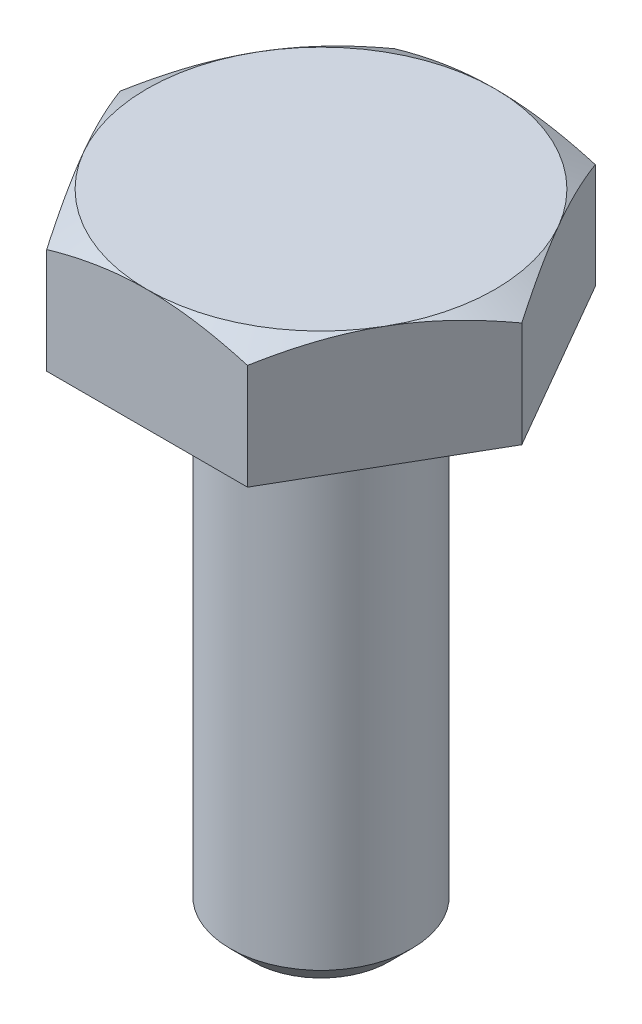
SolidWorks part; units mm, degrees
ref_plane "Front Plane" through (0, 0, 0) normal (0, 0, 1) x (1, 0, 0)
ref_plane "Top Plane" through (0, 0, 0) normal (0, 1, 0) x (1, 0, 0)
ref_plane "Right Plane" through (0, 0, 0) normal (1, 0, 0) x (0, 0, -1)
sketch "Sketch1" plane through (0, 0, 0) normal (0, 1, 0) x (1, 0, 0)
  line L1 (6.6395, 0) -> (3.3198, 5.75)
  line L2 (3.3198, 5.75) -> (-3.3198, 5.75)
  line L3 (-3.3198, 5.75) -> (-6.6395, 0)
  line L4 (-6.6395, 0) -> (-3.3198, -5.75)
  line L5 (-3.3198, -5.75) -> (3.3198, -5.75)
  line L6 (3.3198, -5.75) -> (6.6395, 0)
  circle A1 centre (0, 0) radius 3
extrude "Boss-Extrude2" add sketch "Sketch1" against normal blind 4 contours A1 | L5 L6 L1 L2 L3 L4 A1 region at (4.8275, 0, 2.7872) region at (0, 0, 0)
extrude "Boss-Extrude3" add sketch "Sketch1<7>" against normal blind 21 contours A1 region at (0, 0, 0)
sketch "Sketch1<7>" plane through (0, 0, 0) normal (0, 1, 0) x (1, 0, 0) same geometry as "Sketch1"
cosmetic thread "Cosmetic Thread1" parameters "D1"=10, "D2"=4.891
chamfer "Chamfer2" distance 0.75 angle 45 1 edges at (0, -21, 3)
sketch "Sketch3" plane through (0, 0, 0) normal (0, 1, 0) x (1, 0, 0)
  circle A0 centre (0, 0) radius 5.75
extrude "Cut-Extrude1" cut sketch "Sketch3" against normal blind 21 draft 60 flip side to cut
